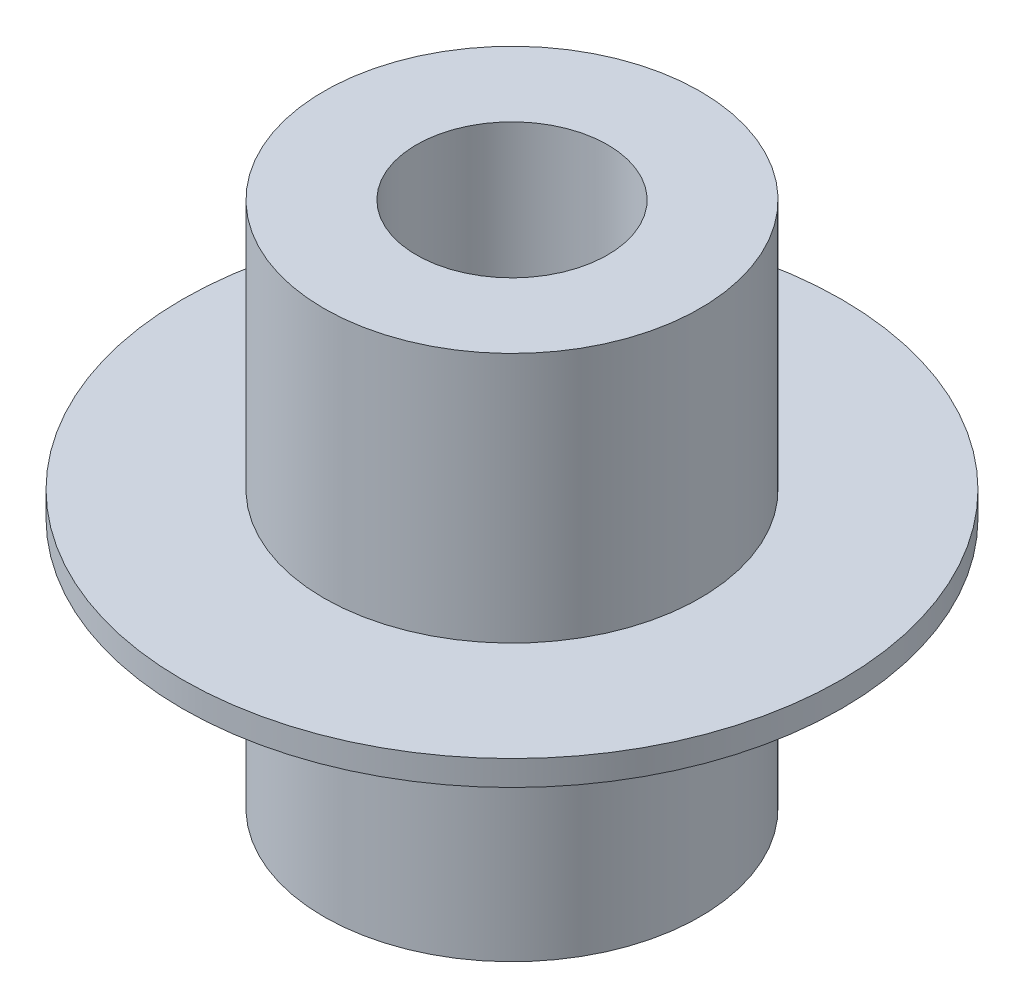
SolidWorks part; units mm, degrees
ref_plane "Front Plane" through (0, 0, 0) normal (0, 0, 1) x (1, 0, 0)
ref_plane "Top Plane" through (0, 0, 0) normal (0, 1, 0) x (1, 0, 0)
ref_plane "Right Plane" through (0, 0, 0) normal (1, 0, 0) x (0, 0, -1)
sketch "Sketch1" plane through (0, 0, 0) normal (0, 0, 1) x (1, 0, 0)
  line L0 (-3.81, -6.2266) -> (-3.81, 14.7734)
  line L13 (-3.81, 14.7734) -> (-7.5, 14.7734)
  line L14 (-7.5, 14.7734) -> (-7.5, 4.7734)
  line L15 (-7.5, 4.7734) -> (-13.1355, 4.7734)
  line L16 (-13.1355, 4.7734) -> (-13.1355, 3.7734)
  line L17 (-13.1355, 3.7734) -> (-7.5, 3.7734)
  line L18 (-7.5, 3.7734) -> (-7.5, -6.2266)
  line L19 (-7.5, -6.2266) -> (-3.81, -6.2266)
  line L20 (0, 0) -> (0, 11.906) construction
  dimension "D1" = 3.81
  dimension "D2" = 7.5
  dimension "D3" = 1
  dimension "D4" = 10
revolve "Revolve1" add sketch "Sketch1" angle 360 about L20
